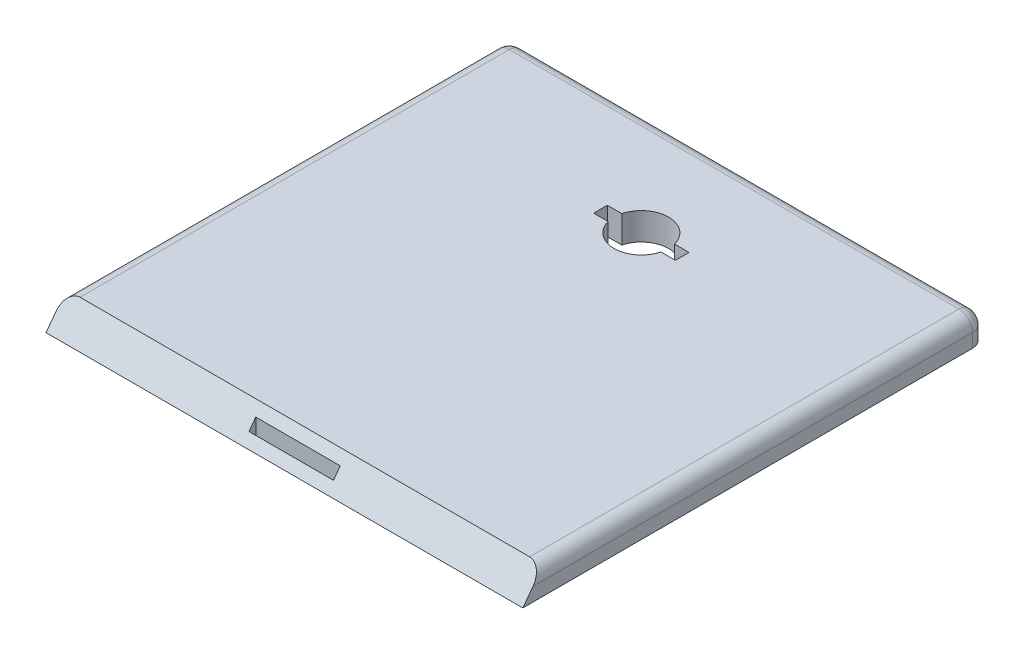
SolidWorks part; units mm, degrees
ref_plane "Ebene vorne" through (0, 0, 0) normal (0, 0, 1) x (1, 0, 0)
ref_plane "Ebene oben" through (0, 0, 0) normal (0, 1, 0) x (1, 0, 0)
ref_plane "Ebene rechts" through (0, 0, 0) normal (1, 0, 0) x (0, 0, -1)
sketch "Skizze1" plane through (0, 0, 0) normal (0, 1, 0) x (1, 0, 0)
  line L1 (-8.75, -8.5) -> (8.75, -8.5)
  line L2 (-8.75, -8.5) -> (-8.75, 8.5)
  line L3 (-8.75, 8.5) -> (8.75, 8.5)
  line L4 (8.75, -8.5) -> (8.75, 8.5)
  line L5 (-8.75, -8.5) -> (8.75, 8.5) construction
  line L6 (-8.75, 8.5) -> (8.75, -8.5) construction
  point P0 (0, 0)
  dimension "D1" = 17
  dimension "D2" = 17.5
extrude "Aufsatz-Linear austragen1" add sketch "Skizze1" along normal blind 1
fillet "Verrundung1" radius 0.5 3 edges at (8.75, 1, 0) (0, 1, -8.5) (-8.75, 1, 0)
sketch "Skizze2" plane through (-8.75, 0, 0) normal (-1, 0, 0) x (0, 0, 1)
  line L0 (8.5, 0) -> (7.75, 1)
  line L1 (-8, 1) -> (8.5, 1) construction
  line L2 (7.75, 1) -> (8.5, 1)
  line L3 (8.5, 1) -> (8.5, 0)
  dimension "D1" = 0.75
extrude "Schnitt-Linear austragen1" cut sketch "Skizze2" against normal up to surface (17.5 mm away) up to face at (8.75, 0.25, 0)
fillet "Verrundung2" radius 0.5 4 edges at (8.6036, 0.8536, -8.3536) (-8.6036, 0.8536, -8.3536) (8.75, 0.25, -8.5) (-8.75, 0.25, -8.5)
sketch "Skizze5" plane through (0, 1, 0) normal (0, 1, 0) x (1, 0, 0)
  line L0 (-8.75, 8) -> (-8.75, -8.5) construction
  line L1 (-1.5, 4.35) -> (1.5, 4.35)
  line L2 (-1.5, 4.35) -> (-1.5, 4.85)
  line L3 (-1.5, 4.85) -> (1.5, 4.85)
  line L4 (1.5, 4.35) -> (1.5, 4.85)
  line L5 (-1.5, 4.35) -> (1.5, 4.85) construction
  line L6 (-1.5, 4.85) -> (1.5, 4.35) construction
  line L7 (-8.25, 8.5) -> (8.25, 8.5) construction
  circle A0 centre (0, 4.6) radius 1
  dimension "D2" = 2
  dimension "D1" = 3
  dimension "D3" = 0.5
  dimension "D4" = 8.75
  dimension "D5" = 3.9
extrude "Schnitt-Linear austragen3" cut sketch "Skizze5" against normal up to surface (1 mm away) contours A0 L3 L2 L1 | L3 A0 | L1 A0 L3 | L1 A0 | A0 L1 L4 L3 region at (-1.2447, 1, -4.6) region at (0, 1, -4.6) region at (0, 1, -4.0376) region at (1.2447, 1, -4.6) region at (0, 1, -5.1624) up to face at (0, 0, -2.7012)
sketch "Skizze6" plane through (0, 1, 0) normal (0, 1, 0) x (1, 0, 0)
  line L0 (8.25, -7.75) -> (-8.25, -7.75) construction
  line L1 (-1.5515, -8.25) -> (1.5515, -8.25)
  line L2 (-1.5515, -8.25) -> (-1.5515, -8)
  line L3 (-1.5515, -8) -> (1.5515, -8)
  line L4 (1.5515, -8.25) -> (1.5515, -8)
  line L5 (-1.5515, -8.25) -> (1.5515, -8) construction
  line L6 (-1.5515, -8) -> (1.5515, -8.25) construction
  line L7 (-8.75, -8.125) -> (-8.75, -8.5) construction
  point P0 (0, -8.125)
  dimension "D1" = 0.25
  dimension "D2" = 0.25
  dimension "D3" = 8.75
extrude "Schnitt-Linear austragen4" cut sketch "Skizze6" against normal up to surface (1 mm away) up to face at (0, 0, -4.6)
